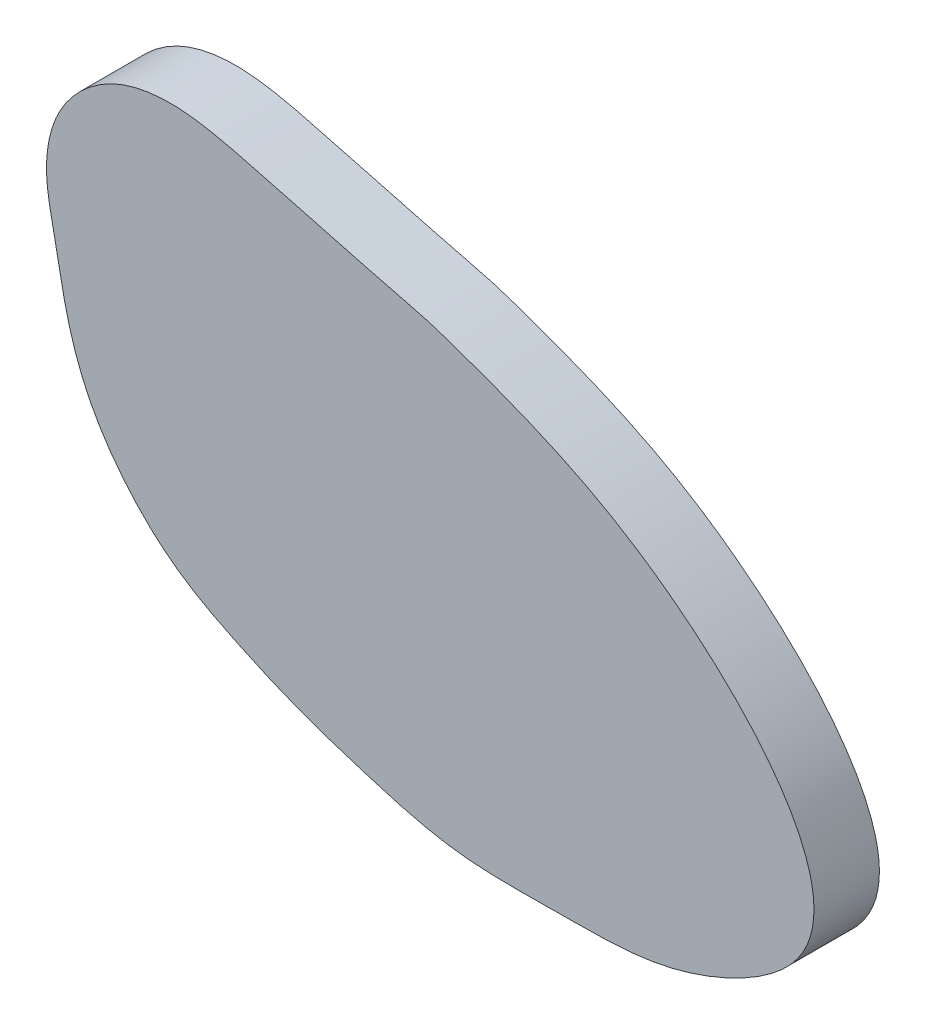
SolidWorks part; units mm, degrees
ref_plane "Front Plane" through (0, 0, 0) normal (0, 0, 1) x (1, 0, 0)
ref_plane "Top Plane" through (0, 0, 0) normal (0, 1, 0) x (1, 0, 0)
ref_plane "Right Plane" through (0, 0, 0) normal (1, 0, 0) x (0, 0, -1)
sketch3d "3DSketch1"
  spline S0 degree 3 poles (56.0719, -23.6179, 0) (34.7135, -0.4593, 0) (17.8078, 6.2665, 0) (9.5895, 9.131, 0) (6.0928, 9.9072, 0) (3.634, 10.5822, 0) (1.17, 11.2382, 0) (-1.2985, 11.8809, 0) (-4.7598, 12.786, 0) (-9.1696, 13.9852, 0) (-14.7192, 15.1752, 0) (-21.4079, 14.1141, 0) (-26.5505, 9.1622, 0) (-27.5158, 2.9318, 0) (-26.2161, -2.5381, 0) (-25.3397, -8.0699, 0) (-23.3309, -13.9157, 0) (-19.6735, -19.4739, 0) (-14.8621, -24.1639, 0) (-8.9458, -27.2347, 0) (-2.9144, -29.9404, 0) (4.439, -32.3087, 0) (12.6463, -34.643, 0) (23.4331, -34.3022, 0) (33.5001, -34.6098, 0) (56.0719, -23.6179, 0) (34.7135, -0.4593, 0) (17.8078, 6.2665, 0) knots -0.304688 -0.242187 -0.179688 0 0.09375 0.117188 0.132812 0.148438 0.15625 0.171875 0.1875 0.210938 0.242188 0.273438 0.3125 0.34375 0.367187 0.398438 0.429688 0.460938 0.5 0.53125 0.5625 0.601562 0.648438 0.695312 0.757813 0.820312 1 1.09375 1.117188 1.132812 only from (30.033, 0, 0) to (30.033, 0, 0)
  point P26 (0, 0, 0)
  point P27 (0, 0, 0)
  point P28 (30.28, -0.2207, 0.2128)
extrude "Boss-Extrude1" add sketch "3DSketch1" along direction (0, 0, 1) on the side of the normal blind 6.35
